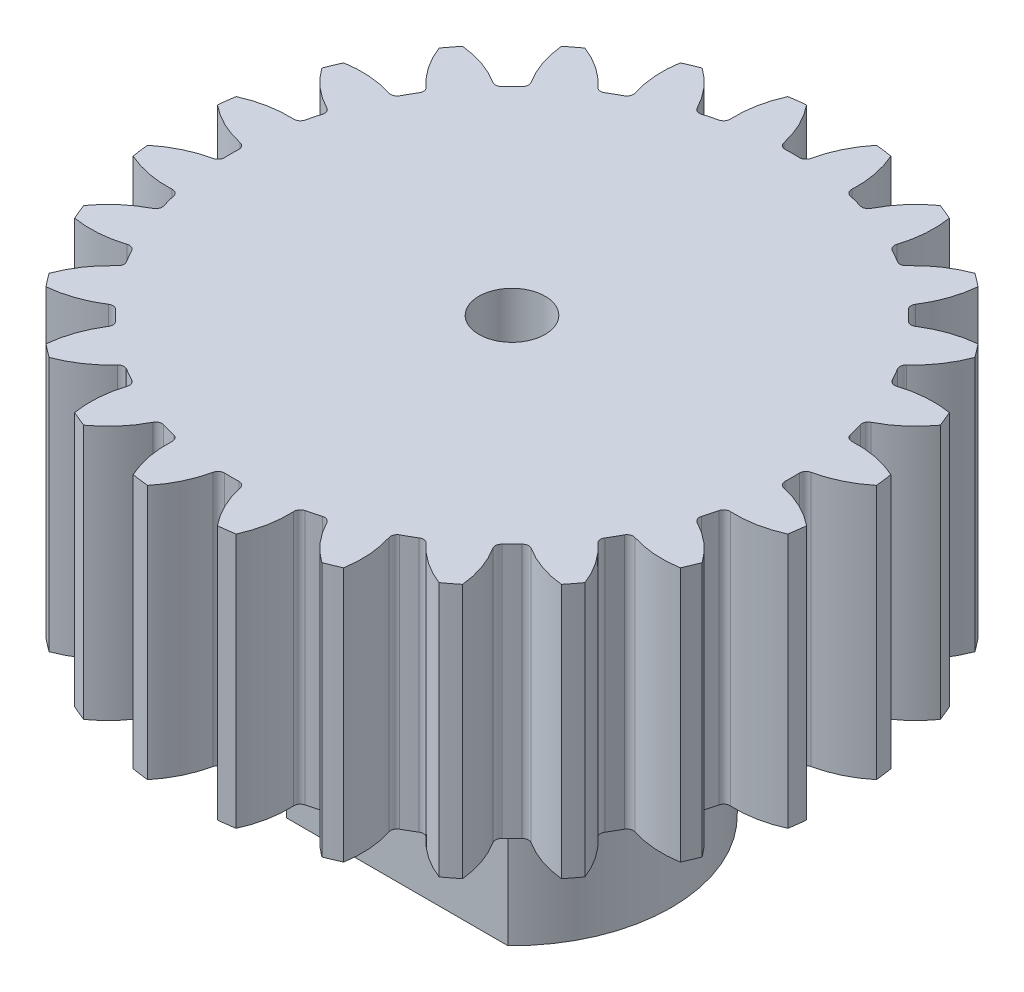
SolidWorks part; units mm, degrees
material "聚脂树脂"
ref_plane "前视基准面" through (0, 0, 0) normal (0, 0, 1) x (1, 0, 0)
ref_plane "上视基准面" through (0, 0, 0) normal (0, 1, 0) x (1, 0, 0)
ref_plane "右视基准面" through (0, 0, 0) normal (1, 0, 0) x (0, 0, -1)
other "Configuration Table"
sketch "草图1" plane through (0, 0, 0) normal (0, 1, 0) x (1, 0, 0)
  circle A0 centre (0, 0) radius 26
  dimension "D1" = 52
extrude "凸台-拉伸1" add sketch "草图1" along normal blind 20
sketch "草图2" plane through (0, 0, 0) normal (0, 1, 0) x (1, 0, 0)
  circle A0 centre (0, 0) radius 12.5
  dimension "D1" = 25
extrude "凸台-拉伸2" add sketch "草图2" against normal blind 14
sketch "草图4" plane through (0, 0, 0) normal (0, 1, 0) x (1, 0, 0)
  line L0 (0, 56.0311) -> (0, -31.5538) construction
  line L1 (0, 0) -> (3.6369, 55.4876) construction
  line L2 (1.5697, 23.9486) -> (26.6905, 22.3021) construction
  line L3 (1.5697, 23.9486) -> (25.0859, 13.6012) construction
  line L4 (9.083, 20.6427) -> (0, 0) construction
  circle A0 centre (0, 0) radius 24 construction
  arc A2 (2.7418, 25.855) -> (1.0619, 22.3865) centre (9.083, 20.6427) ccw
  arc A8 (2.7418, 25.855) -> (-2.7418, 25.855) centre (0, 0) ccw
  circle A9 centre (0, 0) radius 26 construction
  arc A15 (0.5605, 21.9929) -> (-0.5605, 21.9929) centre (0, 0) ccw
  arc A16 (1.0619, 22.3865) -> (0.5605, 21.9929) centre (0.5733, 22.4927) cw
  arc A17 (-1.0619, 22.3865) -> (-0.5605, 21.9929) centre (-0.5733, 22.4927) ccw
  arc A18 (-2.7418, 25.855) -> (-1.0619, 22.3865) centre (-9.083, 20.6427) cw
  dimension "D1" = 48
  dimension "D4" = 22
  dimension "D5" = 0.5
  dimension "D2" = 3.75
  dimension "D3" = 20
extrude "切除-拉伸1" cut sketch "草图4" along normal up to next
pattern_circular "阵列(圆周)1" count 24 over 360 about axis through (0, 20, 0) along (0, 1, 0) of "切除-拉伸1"
sketch "草图6" plane through (0, 0, 0) normal (0, 1, 0) x (1, 0, 0)
  circle A0 centre (0, 0) radius 24 construction
  dimension "D1" = 48
sketch "草图8" plane through (0, 0, 0) normal (0, 0, 1) x (1, 0, 0)
  line L0 (-12.5, -14) -> (12.5, -14) construction
  line L1 (-12.5, -14) -> (12.5, -14)
  line L2 (-12.5, -14) -> (-12.5, 0)
  line L3 (-12.5, 0) -> (12.5, 0)
  line L4 (12.5, -14) -> (12.5, 0)
  line L5 (24, 0) -> (-24, 0) construction
  line L6 (0, -17.9573) -> (0, 22.5638) construction
  dimension "D1" = 25
sketch "草图7" plane through (0, 0, 0) normal (0, 0, 1) x (1, 0, 0)
  line L0 (0, 37.4487) -> (0, -32.2732) construction
  line L1 (-12.5, -14) -> (12.5, -14) construction
  circle A0 centre (-4, -7) radius 2.15
  circle A1 centre (4.5, -7) radius 2.15
  dimension "D1" = 4.3
  dimension "D2" = 4.5
  dimension "D3" = 7
  dimension "D4" = 4
extrude "切除-拉伸4" cut sketch "草图7" against normal through all both and the other way through all
sketch "草图5" plane through (0, 0, 0) normal (0, 1, 0) x (1, 0, 0)
  circle A0 centre (0, 0) radius 2.6
  dimension "D1" = 5.2
extrude "切除-拉伸2" cut sketch "草图5" against normal through all both and the other way through all
extrude "切除-拉伸5" cut sketch "草图8" along normal blind 3.5 from offset 12.5 offset against normal yes
extrude "切除-拉伸6" cut sketch "草图8<2>" against normal blind 3.5 from offset 12.5
sketch "草图8<2>" plane through (0, 0, 0) normal (0, 0, 1) x (1, 0, 0) same geometry as "草图8"
